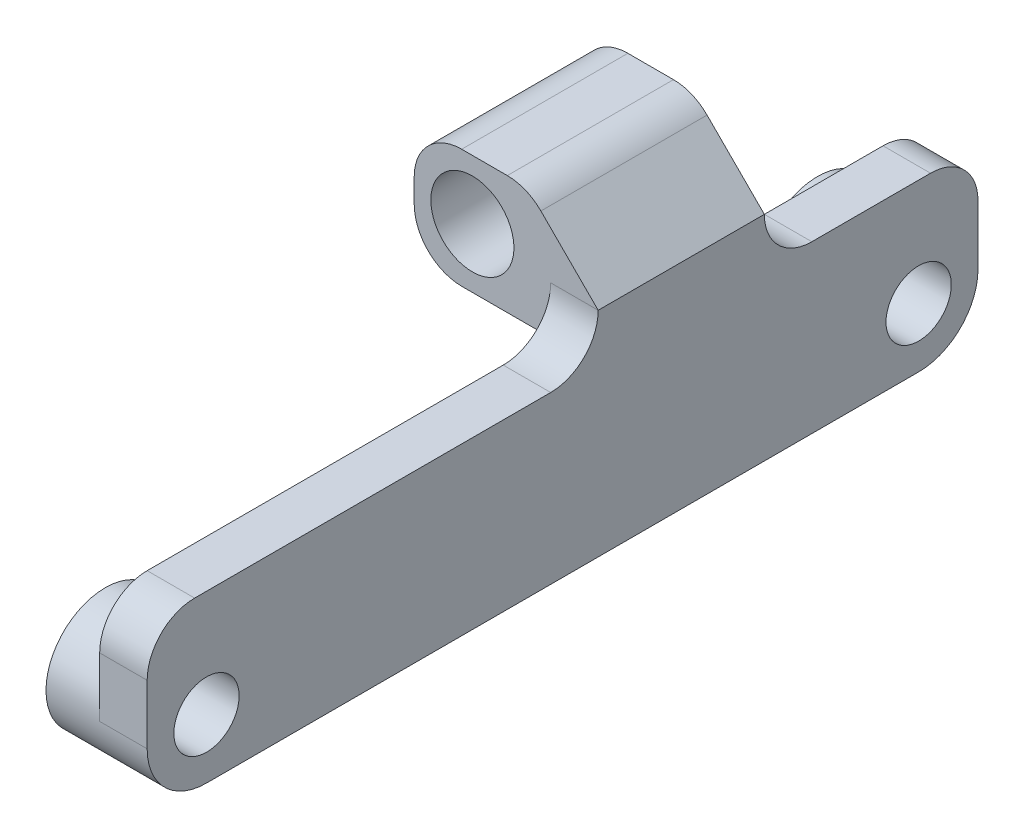
SolidWorks part; units mm, degrees
ref_plane "Front Plane" through (0, 0, 0) normal (0, 0, 1) x (1, 0, 0)
ref_plane "Top Plane" through (0, 0, 0) normal (0, 1, 0) x (1, 0, 0)
ref_plane "Right Plane" through (0, 0, 0) normal (1, 0, 0) x (0, 0, -1)
sketch "Sketch1" plane through (0, 0, 0) normal (1, 0, 0) x (0, 0, -1)
  circle A0 centre (30, 0) radius 5
  circle A1 centre (-30, 0) radius 5
  dimension "D1" = 2
extrude "Boss-Extrude1" add sketch "Sketch1" along normal blind 5.1
sketch "Sketch2" plane through (5.1, 0, 0) normal (1, 0, 0) x (0, 0, -1)
  line L1 (30, -5) -> (-30, -5)
  line L3 (-35, 0) -> (-35, 5)
  line L4 (-35, 5) -> (-35, 9)
  line L6 (35, 9) -> (35, 0)
  line L8 (35, 9) -> (-35, 9)
  circle A0 centre (-30, 0) radius 5 construction
  circle A1 centre (30, 0) radius 5 construction
  arc A2 (-35, 0) -> (-30, -5) centre (-30, 0) ccw
  arc A3 (30, -5) -> (35, 0) centre (30, 0) ccw
extrude "Boss-Extrude2" add sketch "Sketch2" along normal blind 4
sketch "Sketch3" plane through (0, 9, 0) normal (0, 1, 0) x (1, 0, 0)
  line L2 (5.1, 17) -> (-4.9, 17)
  line L3 (-4.9, 17) -> (-6.4, 17)
  line L4 (9.1, 17) -> (5.1, 17)
  line L6 (-4.9, 3) -> (9.1, 3)
  line L8 (9.1, 3) -> (9.1, 17)
  line L10 (-6.4, 3) -> (-4.9, 3)
  line L12 (-6.4, 3) -> (-6.4, 17)
extrude "Boss-Extrude3" add sketch "Sketch3" along normal blind 4
sketch "Sketch4" plane through (0, 13, 0) normal (0, 1, 0) x (1, 0, 0)
  line L8 (9.1, 17) -> (-6.4, 17) construction
  line L9 (3.1, 17) -> (-6.4, 17)
  line L13 (3.1, 10) -> (3.1, 17)
  line L16 (-6.4, 3) -> (9.1, 3) construction
  line L17 (3.1, 3) -> (3.1, 10)
  line L18 (3.1, 3) -> (-6.4, 3)
  line L20 (-6.4, 3) -> (-6.4, 17)
  point P3 (3.8953, 15)
extrude "Boss-Extrude4" add sketch "Sketch4" along normal blind 6
sketch "Sketch5" plane through (0, 0, -17) normal (0, 0, 1) x (1, 0, 0)
  circle A0 centre (-1.5, 14) radius 3.5
extrude "Cut-Extrude1" cut sketch "Sketch5" along normal through all
sketch "Sketch6" plane through (0, 0, -17) normal (0, 0, -1) x (-1, 0, 0)
  line L1 (1.5, 9) -> (5.8301, 11.5)
  line L2 (5.8301, 11.5) -> (5.8301, 16.5)
  line L3 (5.8301, 16.5) -> (1.5, 19)
  line L4 (1.5, 19) -> (-2.8301, 16.5)
  line L5 (-2.8301, 16.5) -> (-2.8301, 11.5)
  line L6 (-2.8301, 11.5) -> (1.5, 9)
  circle A0 centre (1.5, 14) radius 5 construction
sketch "Sketch7" plane through (0, 0, 0) normal (-1, 0, 0) x (0, 0, 1)
  circle A0 centre (-30, 0) radius 2.75
  circle A1 centre (30, 0) radius 2.75
extrude "Cut-Extrude2" cut sketch "Sketch7" against normal through all
sketch "Sketch8" plane through (0, 0, -17) normal (0, 0, -1) x (-1, 0, 0)
  line L0 (-9.1, 13) -> (-3.1, 19)
  line L1 (-3.1, 19) -> (-3.1, 13)
  line L2 (-3.1, 13) -> (-9.1, 13)
extrude "Boss-Extrude5" add sketch "Sketch8" against normal up to surface (14 mm away) up to face at (-5, 14, -3)
fillet "Fillet1" radius 4 3 edges at (-6.4, 9, -10) (-6.4, 19, -10) (3.1, 19, -10)
fillet "Fillet2" radius 4 2 edges at (7.1, 9, -3) (7.1, 9, -17)
fillet "Fillet3" radius 4 2 edges at (7.1, 9, -35) (7.1, 9, 35)
chamfer "Chamfer1" distance 1 angle 30 2 edges at (0, 0, 25) (0, 0, -35) first distance on face at (0, 0, 32.75) first distance on face at (0, 0, -27.25)
